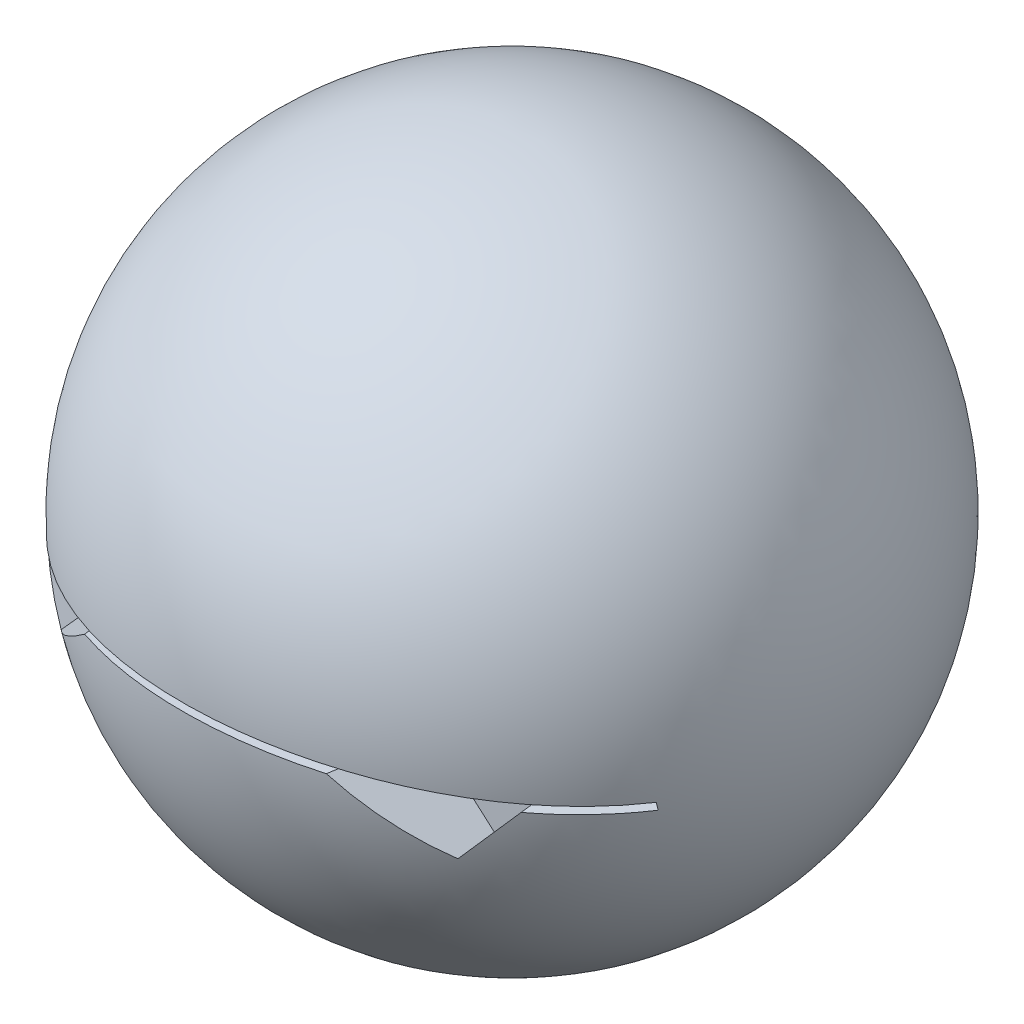
SolidWorks part; units mm, degrees
note: '?' marks a value the reader was unsure of.
material "Polybutadiène (PB)"
ref_plane "Plan de face" through (0, 0, 0) normal (0, 0, 1) x (1, 0, 0)
ref_plane "Plan de dessus" through (0, 0, 0) normal (0, 1, 0) x (1, 0, 0)
ref_plane "Plan de droite" through (0, 0, 0) normal (1, 0, 0) x (0, 0, -1)
sketch "Esquisse1" plane through (0, 0, 0) normal (0, 0, 1) x (1, 0, 0)
  line L0 (0, -3.5459) -> (0, 5.5111)
  arc A0 (0, 10.6989) -> (0, -10.6989) centre (0, 0) cw
revolve "Révol.-Mince1" add sketch "Esquisse1" angle 360 about L0
sketch "Esquisse2" plane through (0, 0, 0) normal (0, 0, 1) x (1, 0, 0)
  line L0 (-9.4989, -1.25) -> (-9.5, -1)
  line L1 (9.5011, -1.25) -> (9.5, -1)
  spline S0 degree 2 poles (-9.5, -1) (0, 1) (9.5, -1) knots 0 0 0 1 1 1
  spline S1 degree 2 poles (-9.4989, -1.25) (0.0011, 0.7501) (9.5011, -1.25) knots 0 0 0 1 1 1
  dimension "D3" = 0
  dimension "D5" = 9.5
  dimension "D1" = 1
  dimension "D2" = 1
  dimension "D4" = 9.5
  dimension "D6" = 0.25
  dimension "D7" = 0.25
extrude "Enlèv. mat.-Extru.2" cut sketch "Esquisse2" along normal through all
ref_plane "Plan1" through (0, 0, 10) normal (0, 0, 1) x (1, 0, 0)
sketch "Esquisse4" plane through (0, 0, 10) normal (0, 0, 1) x (1, 0, 0)
  line L0 (0, 0) -> (0, -4.4331)
  line L1 (3.7197, -0.25) -> (6.4523, -2.6527)
  line L2 (6.4523, -2.6527) -> (8.2133, -0.65)
  line L3 (8.2133, -0.65) -> (3.7197, -0.25)
  line L4 (-6.4523, -2.6527) -> (-8.2133, -0.65)
  line L5 (-3.7197, -0.25) -> (-6.4523, -2.6527)
  line L6 (-8.2133, -0.65) -> (-3.7197, -0.25)
  point P5 (0, 0)
  point P6 (0, 0)
  point P7 (0, 0)
  point P8 (0, 0)
  point P17 (4.2501, -0.45)
  point P18 (0, 0)
  point P19 (0, 0)
  point P20 (0, 0)
  point P21 (0, 0)
  dimension "D1" = 0.25
  dimension "D2" = 2.6527
  dimension "D3" = 0.65
extrude "Enlèv. mat.-Extru.4" cut sketch "Esquisse4" against normal blind 3 draft 5 contours L1 L2 L3 | L5 L4 L6
ref_plane "Plan2" through (0, 0, 4) normal (0, 0, 1) x (1, 0, 0)
sketch "Esquisse9" plane through (0, 0, 4) normal (0, 0, 1) x (1, 0, 0)
  line L0 (9.5, -1) -> (9.5011, -1.25)
ref_axis "Axe1" through (0, -3.5459, 0) along (0, 1, 0)?
sketch3d "Esquisse3D4"
  line L0 (9.5011, -1.25, 4) -> (9.5, -1, 4)
  line L1 (0, -3.5459, 0) -> (0, 5.5111, 0)
ref_plane "Plan3" through (0, 0, 0) normal (-0.388, 0, 0.9217) x (0.9217, 0, 0.388)
sketch "Esquisse11" plane through (0, 0, 0) normal (0, 0, 1) x (1, 0, 0)
  arc A0 (10.1476, -2.5282) -> (10.3625, 1.4088) centre (0, 0) ccw
